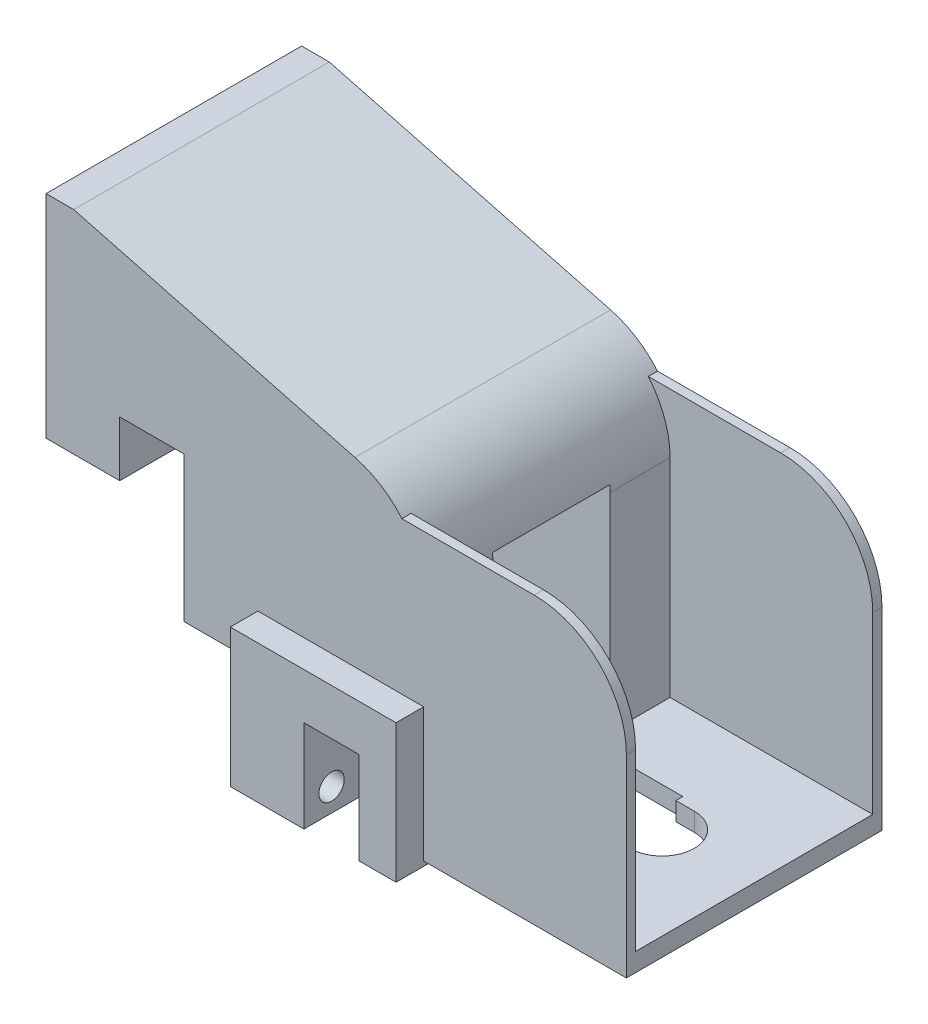
SolidWorks part; units mm, degrees
ref_plane "Front Plane" through (0, 0, 0) normal (0, 0, 1) x (1, 0, 0)
ref_plane "Top Plane" through (0, 0, 0) normal (0, 1, 0) x (1, 0, 0)
ref_plane "Right Plane" through (0, 0, 0) normal (1, 0, 0) x (0, 0, -1)
sketch "Sketch1" plane through (0, 0, 0) normal (0, 1, 0) x (1, 0, 0)
  line L1 (-17.3014, 15.4212) -> (30.6986, 15.4212)
  line L2 (-17.3014, 15.4212) -> (-17.3014, -12.3288)
  line L3 (-17.3014, -12.3288) -> (30.6986, -12.3288)
  line L4 (30.6986, 15.4212) -> (30.6986, -12.3288)
  dimension "D1" = 27.75
  dimension "D2" = 48
extrude "Boss-Extrude1" add sketch "Sketch1" along normal blind 31
sketch "Sketch2" plane through (-17.3014, 0, 0) normal (-1, 0, 0) x (0, 0, 1)
  line L1 (-7.9212, 25.25) -> (4.8288, 25.25)
  line L2 (-7.9212, 25.25) -> (-7.9212, 2)
  line L3 (-7.9212, 2) -> (-5.7962, 2)
  line L4 (4.8288, 25.25) -> (4.8288, 2)
  line L5 (-15.4212, 0) -> (12.3288, 0) construction
  line L6 (2.7038, 2) -> (4.8288, 2)
  line L8 (-5.7962, 2) -> (-5.7962, 0)
  line L9 (-5.7962, 0) -> (2.7038, 0)
  line L10 (2.7038, 2) -> (2.7038, 0)
  line L11 (-15.4212, 31) -> (12.3288, 31) construction
  point P4 (-1.5462, 25.25)
  point P13 (-1.5462, 0)
  point P14 (-1.5462, 31)
  dimension "D1" = 2
  dimension "D2" = 12.75
  dimension "D3" = 8.5
  dimension "D4" = 23.25
extrude "Cut-Extrude1" cut sketch "Sketch2" against normal blind 36
sketch "Sketch3" plane through (0, 31, 0) normal (0, 1, 0) x (1, 0, 0)
  line L0 (30.6986, -12.3288) -> (30.6986, 15.4212) construction
  line L1 (30.6986, 14.4212) -> (8.6986, 14.4212)
  line L2 (30.6986, 14.4212) -> (30.6986, -11.3288)
  line L3 (30.6986, -11.3288) -> (8.6986, -11.3288)
  line L4 (8.6986, 14.4212) -> (8.6986, -11.3288)
  point P6 (30.6986, 1.5462)
  point P7 (30.6986, 1.5462)
  dimension "D1" = 22
  dimension "D2" = 25.75
extrude "Cut-Extrude2" cut sketch "Sketch3" against normal offset from surface (29 mm away) 2 up to face at (3.6986, 0, -1.5462)
sketch "Sketch4" plane through (0, 2, 0) normal (0, 1, 0) x (1, 0, 0)
  line L0 (30.6986, 14.4212) -> (30.6986, -11.3288) construction
  line L1 (8.6986, 14.4212) -> (30.6986, 14.4212) construction
  line L2 (20.6986, -1.9538) -> (18.6986, -1.9538)
  line L3 (20.6986, 5.0462) -> (18.6986, 5.0462)
  arc A0 (18.6986, 5.0462) -> (18.6986, -1.9538) centre (18.6986, 1.5462) ccw
  arc A1 (20.6986, -1.9538) -> (20.6986, 5.0462) centre (20.6986, 1.5462) ccw
  point P5 (30.6986, 1.5462)
  point P8 (19.6986, 14.4212)
  point P10 (19.6986, 1.5462)
  dimension "D1" = 7
  dimension "D2" = 1
  dimension "D3" = 1
extrude "Cut-Extrude3" cut sketch "Sketch4" against normal through all contours A0 L2 A1 L3
sketch "Sketch5" plane through (-17.3014, 0, 0) normal (-1, 0, 0) x (0, 0, 1)
  line L0 (4.8288, 25.25) -> (-7.9212, 25.25) construction
  line L1 (-15.4212, 42.25) -> (12.3288, 42.25)
  line L2 (-15.4212, 42.25) -> (-15.4212, 25.25)
  line L3 (-15.4212, 25.25) -> (12.3288, 25.25)
  line L4 (12.3288, 42.25) -> (12.3288, 25.25)
  line L5 (-15.4212, 31) -> (12.3288, 31) construction
  line L6 (-15.4212, 31) -> (-15.4212, 0) construction
  point P6 (-1.5462, 25.25)
  point P9 (-1.5462, 31)
  dimension "D1" = 17
extrude "Boss-Extrude2" add sketch "Sketch5" along normal blind 15 and the other way up to surface (26 mm away) other way up to face at (8.6986, 15.0625, -1.5462)
sketch "Sketch10" plane through (-32.3014, 0, 0) normal (-1, 0, 0) x (0, 0, 1)
  line L0 (12.3288, 25.25) -> (12.3288, 42.25) construction
  line L1 (-15.4212, 42.25) -> (12.3288, 42.25)
  line L2 (-15.4212, 42.25) -> (-15.4212, 19.25)
  line L3 (-15.4212, 19.25) -> (12.3288, 19.25)
  line L4 (12.3288, 42.25) -> (12.3288, 19.25)
  line L5 (-15.4212, 25.25) -> (12.3288, 25.25) construction
  dimension "D1" = 6
extrude "Boss-Extrude4" add sketch "Sketch10" against normal blind 8 contours L3 L4 L1 L2
chamfer "Chamfer1" distance 38 distance2 10 1 edges at (8.6986, 42.25, -1.5462) first distance on face at (-11.8014, 42.25, -1.5462)
fillet "Fillet1" radius 10 3 edges at (30.6986, 31, -14.9212) (30.6986, 31, 11.8288) (8.6986, 32.25, -1.5462)
sketch "Sketch6" plane through (-17.3014, 0, 0) normal (-1, 0, 0) x (0, 0, 1)
  line L1 (4.8288, 2) -> (4.8288, 25.25) construction
  line L3 (6.3288, 9.5) -> (15.3288, 9.5)
  line L4 (6.3288, 9.5) -> (6.3288, 0)
  line L5 (6.3288, 0) -> (15.3288, 0)
  line L6 (15.3288, 9.5) -> (15.3288, 0)
  line L7 (2.7038, 0) -> (12.3288, 0) construction
  line L8 (12.3288, 25.25) -> (12.3288, 0) construction
  dimension "D1" = 3
  dimension "D4" = 1.5
  dimension "D5" = 9.5
extrude "Cut-Extrude4" cut sketch "Sketch6" against normal offset from surface (8 mm away) 18
sketch "Sketch7" plane through (-9.3014, 0, 0) normal (-1, 0, 0) x (0, 0, 1)
  line L0 (12.3288, 0) -> (12.3288, 9.5) construction
  line L1 (12.3288, 0) -> (12.3288, 9.5)
  line L3 (6.3288, 0) -> (12.3288, 0)
  line L4 (15.3288, 9.5) -> (6.3288, 9.5)
  line L5 (15.3288, 0) -> (15.3288, 9.5)
  line L6 (6.3288, 0) -> (15.3288, 0)
  line L7 (6.3288, 9.5) -> (6.3288, 0)
  line L9 (15.3288, 0) -> (15.3288, 9.5)
  line L12 (6.3288, 0) -> (6.3288, -0.5)
  line L13 (6.3288, -0.5) -> (15.3288, -0.5)
  line L14 (15.3288, 0) -> (15.3288, -0.5)
  line L18 (15.3288, 9.5) -> (15.3288, 14.5)
  line L19 (15.3288, 14.5) -> (12.3288, 14.5)
  line L20 (12.3288, 9.5) -> (12.3288, 14.5)
  dimension "D2" = 0.5
  dimension "D3" = 5
  dimension "D1" = 0
extrude "Boss-Extrude3" add sketch "Sketch7" against normal up to surface (18 mm away)
sketch "Sketch8" plane through (-9.3014, 0, 0) normal (-1, 0, 0) x (0, 0, 1)
  line L1 (4.8288, 2) -> (4.8288, 25.25) construction
  line L2 (2.7038, 0) -> (6.3288, 0) construction
  circle A0 centre (12.3288, 2) radius 1.375
  dimension "D3" = 2.75
  dimension "D1" = 2
  dimension "D2" = 7.5
extrude "Cut-Extrude5" cut sketch "Sketch8" against normal offset from surface (17 mm away) 1
sketch "Sketch9" plane through (0, 0, 15.3288) normal (0, 0, 1) x (1, 0, 0)
  line L1 (-1.3014, 9.5) -> (4.6986, 9.5)
  line L2 (-1.3014, 9.5) -> (-1.3014, -0.5)
  line L3 (-1.3014, -0.5) -> (4.6986, -0.5)
  line L4 (4.6986, 9.5) -> (4.6986, -0.5)
  line L5 (8.6986, -0.5) -> (-9.3014, -0.5) construction
  line L6 (8.6986, 14.5) -> (8.6986, -0.5) construction
  line L7 (-17.3014, 9.5) -> (-9.3014, 9.5) construction
  dimension "D1" = 6
  dimension "D2" = 4
extrude "Cut-Extrude6" cut sketch "Sketch9" against normal up to surface (9 mm away) up to face at (-13.3014, 4.75, 6.3288)
ref_plane "Plane1" through (0, 0, -1.5462) normal (0, 0, 1) x (1, 0, 0)
mirror "Mirror1" about plane through (0, 0, -1.5462) normal (0, 0, 1) of "Cut-Extrude6", "Cut-Extrude5", "Boss-Extrude3", "Cut-Extrude4"
